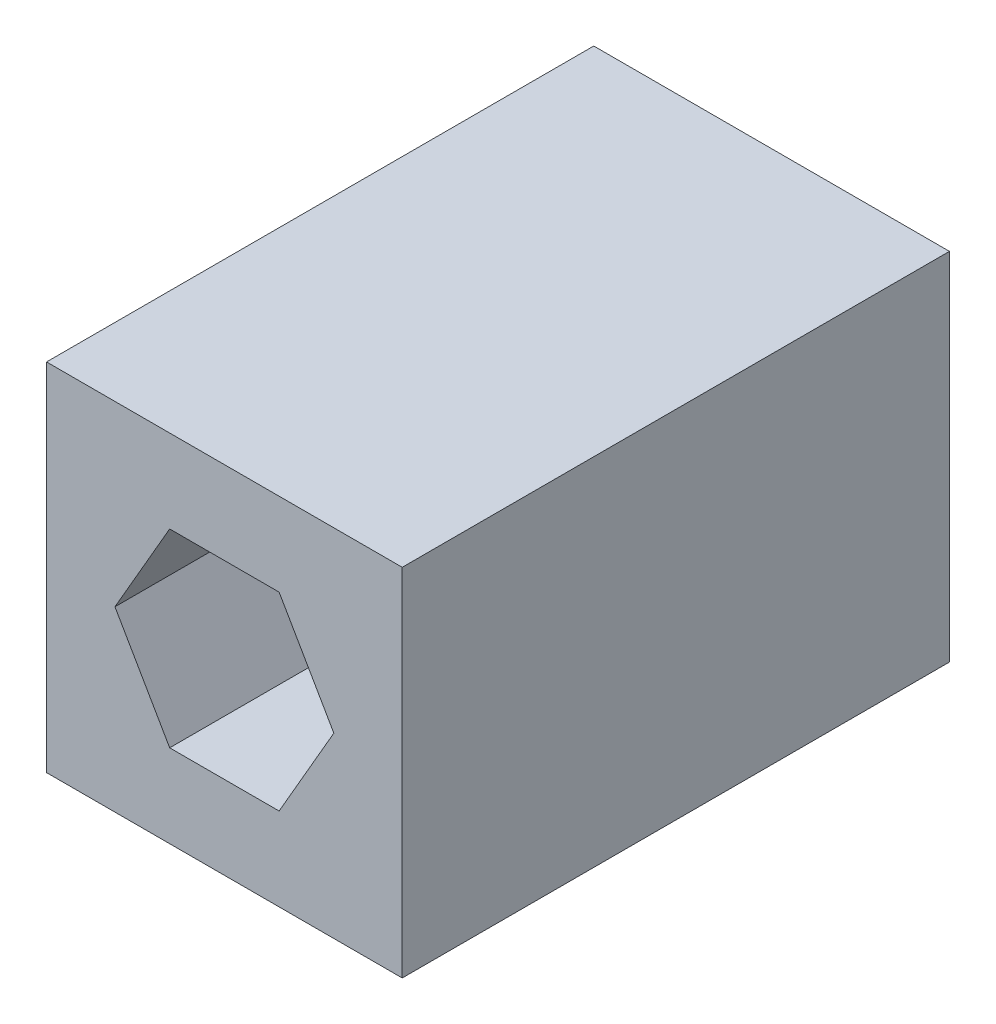
SolidWorks part; units mm, degrees
ref_plane "정면" through (0, 0, 0) normal (0, 0, 1) x (1, 0, 0)
ref_plane "윗면" through (0, 0, 0) normal (0, 1, 0) x (1, 0, 0)
ref_plane "우측면" through (0, 0, 0) normal (1, 0, 0) x (0, 0, -1)
ref_axis "기준축2" through (0, 0, 210) along (0, 0, -1)
ref_axis "기준축4" through (0, 55, 0) along (0, -1, 0)
sketch "스케치1" plane through (0, 0, 0) normal (0, 0, 1) x (1, 0, 0)
  line L1 (35, 0) -> (17.5, 30.3109)
  line L2 (17.5, 30.3109) -> (-17.5, 30.3109)
  line L3 (-17.5, 30.3109) -> (-35, 0)
  line L4 (-35, 0) -> (-17.5, -30.3109)
  line L5 (-17.5, -30.3109) -> (17.5, -30.3109)
  line L6 (17.5, -30.3109) -> (35, 0)
  circle A0 centre (0, 0) radius 35 construction
  dimension "D1" = 70
extrude "보스-돌출1" [suppressed] add sketch "스케치1" along normal blind 200
sketch "스케치2" plane through (0, 0, 0) normal (0, 0, 1) x (1, 0, 0)
  line L1 (-65, 65) -> (65, 65)
  line L2 (-65, 65) -> (-65, -65)
  line L3 (-65, -65) -> (65, -65)
  line L4 (65, 65) -> (65, -65)
  line L6 (20, 34.641) -> (-20, 34.641)
  line L7 (-20, 34.641) -> (-40, 0)
  line L8 (-40, 0) -> (-20, -34.641)
  line L9 (-20, -34.641) -> (20, -34.641)
  line L10 (20, -34.641) -> (40, 0)
  line L11 (40, 0) -> (20, 34.641)
  circle A0 centre (0, 0) radius 40 construction
  point P4 (0, -65)
  point P6 (65, 0)
  dimension "D3" = 80
  dimension "D1" = 130
  dimension "D2" = 130
extrude "보스-돌출2" add sketch "스케치2" along normal blind 200 separate body
